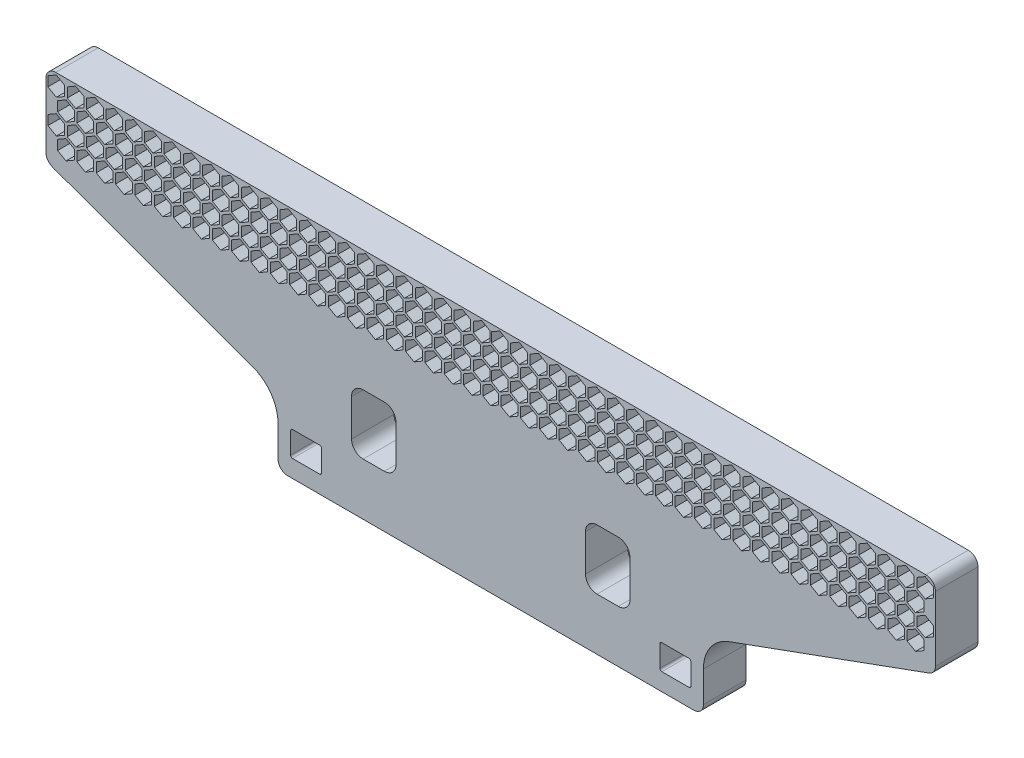
SolidWorks part; units mm, degrees
ref_plane "Front Plane" through (0, 0, 0) normal (0, 0, 1) x (1, 0, 0)
ref_plane "Top Plane" through (0, 0, 0) normal (0, 1, 0) x (1, 0, 0)
ref_plane "Right Plane" through (0, 0, 0) normal (1, 0, 0) x (0, 0, -1)
sketch "Sketch1" plane through (0, 0, 0) normal (0, 0, 1) x (1, 0, 0)
  line L0 (0, 0) -> (0, -38.3146) construction
  line L1 (-69.85, 38.3146) -> (69.85, 38.3146)
  line L2 (-69.85, 38.3146) -> (-69.85, -38.3146)
  line L3 (-69.85, -38.3146) -> (69.85, -38.3146)
  line L4 (69.85, 38.3146) -> (69.85, -38.3146)
  line L5 (-69.85, 38.3146) -> (69.85, -38.3146) construction
  line L6 (-69.85, -38.3146) -> (69.85, 38.3146) construction
  line L7 (65.7225, -32.5996) -> (55.5625, -32.5996)
  line L8 (-65.7225, -24.3446) -> (-55.5625, -24.3446)
  line L9 (-65.7225, -24.3446) -> (-65.7225, -32.5996)
  line L10 (-65.7225, -32.5996) -> (-55.5625, -32.5996)
  line L11 (-55.5625, -24.3446) -> (-55.5625, -32.5996)
  line L12 (-65.7225, -24.3446) -> (-55.5625, -32.5996) construction
  line L13 (-65.7225, -32.5996) -> (-55.5625, -24.3446) construction
  line L14 (55.5625, -24.3446) -> (55.5625, -32.5996)
  line L15 (65.7225, -24.3446) -> (55.5625, -24.3446)
  line L16 (65.7225, -24.3446) -> (65.7225, -32.5996)
  line L17 (41.91, -21.1696) -> (34.925, -21.1696)
  line L18 (-41.91, -1.4846) -> (-34.925, -1.4846)
  line L19 (-45.72, -5.2946) -> (-45.72, -17.3596)
  line L20 (-41.91, -21.1696) -> (-34.925, -21.1696)
  line L21 (-31.115, -5.2946) -> (-31.115, -17.3596)
  line L22 (-45.72, -1.4846) -> (-31.115, -21.1696) construction
  line L23 (-45.72, -21.1696) -> (-31.115, -1.4846) construction
  line L24 (31.115, -5.2946) -> (31.115, -17.3596)
  line L25 (41.91, -1.4846) -> (34.925, -1.4846)
  line L26 (-69.85, 38.3146) -> (-69.85, -38.3146)
  line L27 (69.85, 38.3146) -> (69.85, -38.3146)
  line L28 (45.72, -5.2946) -> (45.72, -17.3596)
  line L29 (69.85, -16.0896) -> (146.05, 11.645)
  line L31 (146.05, 11.645) -> (146.05, 38.3146)
  line L32 (146.05, 38.3146) -> (69.85, 38.3146)
  line L33 (0, -38.3146) -> (0, 38.3146) construction
  line L34 (139.9157, 36.0921) -> (142.6654, 37.6796)
  line L35 (142.6654, 37.6796) -> (145.415, 36.0921)
  line L36 (145.415, 36.0921) -> (145.415, 32.9171)
  line L37 (145.415, 32.9171) -> (142.6654, 31.3296)
  line L38 (142.6654, 31.3296) -> (139.9157, 32.9171)
  line L39 (139.9157, 32.9171) -> (139.9157, 36.0921)
  line L40 (146.05, 11.645) -> (69.85, 11.645) construction
  line L41 (69.85, 11.645) -> (0, 11.645) construction
  line L43 (133.5657, 36.0921) -> (136.3154, 37.6796)
  line L44 (133.5657, 32.9171) -> (133.5657, 36.0921)
  line L45 (136.3154, 31.3296) -> (133.5657, 32.9171)
  line L46 (139.065, 32.9171) -> (136.3154, 31.3296)
  line L47 (139.065, 36.0921) -> (139.065, 32.9171)
  line L48 (136.3154, 37.6796) -> (139.065, 36.0921)
  line L49 (127.2157, 36.0921) -> (129.9654, 37.6796)
  line L50 (127.2157, 32.9171) -> (127.2157, 36.0921)
  line L51 (129.9654, 31.3296) -> (127.2157, 32.9171)
  line L52 (132.715, 32.9171) -> (129.9654, 31.3296)
  line L53 (132.715, 36.0921) -> (132.715, 32.9171)
  line L54 (129.9654, 37.6796) -> (132.715, 36.0921)
  line L55 (120.8657, 36.0921) -> (123.6154, 37.6796)
  line L56 (120.8657, 32.9171) -> (120.8657, 36.0921)
  line L57 (123.6154, 31.3296) -> (120.8657, 32.9171)
  line L58 (126.365, 32.9171) -> (123.6154, 31.3296)
  line L59 (126.365, 36.0921) -> (126.365, 32.9171)
  line L60 (123.6154, 37.6796) -> (126.365, 36.0921)
  line L61 (114.5157, 36.0921) -> (117.2654, 37.6796)
  line L62 (114.5157, 32.9171) -> (114.5157, 36.0921)
  line L63 (117.2654, 31.3296) -> (114.5157, 32.9171)
  line L64 (120.015, 32.9171) -> (117.2654, 31.3296)
  line L65 (120.015, 36.0921) -> (120.015, 32.9171)
  line L66 (117.2654, 37.6796) -> (120.015, 36.0921)
  line L67 (108.1657, 36.0921) -> (110.9154, 37.6796)
  line L68 (108.1657, 32.9171) -> (108.1657, 36.0921)
  line L69 (110.9154, 31.3296) -> (108.1657, 32.9171)
  line L70 (113.665, 32.9171) -> (110.9154, 31.3296)
  line L71 (113.665, 36.0921) -> (113.665, 32.9171)
  line L72 (110.9154, 37.6796) -> (113.665, 36.0921)
  line L73 (101.8157, 36.0921) -> (104.5654, 37.6796)
  line L74 (101.8157, 32.9171) -> (101.8157, 36.0921)
  line L75 (104.5654, 31.3296) -> (101.8157, 32.9171)
  line L76 (107.315, 32.9171) -> (104.5654, 31.3296)
  line L77 (107.315, 36.0921) -> (107.315, 32.9171)
  line L78 (104.5654, 37.6796) -> (107.315, 36.0921)
  line L79 (95.4657, 36.0921) -> (98.2154, 37.6796)
  line L80 (95.4657, 32.9171) -> (95.4657, 36.0921)
  line L81 (98.2154, 31.3296) -> (95.4657, 32.9171)
  line L82 (100.965, 32.9171) -> (98.2154, 31.3296)
  line L83 (100.965, 36.0921) -> (100.965, 32.9171)
  line L84 (98.2154, 37.6796) -> (100.965, 36.0921)
  line L85 (89.1157, 36.0921) -> (91.8654, 37.6796)
  line L86 (89.1157, 32.9171) -> (89.1157, 36.0921)
  line L87 (91.8654, 31.3296) -> (89.1157, 32.9171)
  line L88 (94.615, 32.9171) -> (91.8654, 31.3296)
  line L89 (94.615, 36.0921) -> (94.615, 32.9171)
  line L90 (91.8654, 37.6796) -> (94.615, 36.0921)
  line L91 (82.7657, 36.0921) -> (85.5154, 37.6796)
  line L92 (82.7657, 32.9171) -> (82.7657, 36.0921)
  line L93 (85.5154, 31.3296) -> (82.7657, 32.9171)
  line L94 (88.265, 32.9171) -> (85.5154, 31.3296)
  line L95 (88.265, 36.0921) -> (88.265, 32.9171)
  line L96 (85.5154, 37.6796) -> (88.265, 36.0921)
  line L97 (76.4157, 36.0921) -> (79.1654, 37.6796)
  line L98 (76.4157, 32.9171) -> (76.4157, 36.0921)
  line L99 (79.1654, 31.3296) -> (76.4157, 32.9171)
  line L100 (81.915, 32.9171) -> (79.1654, 31.3296)
  line L101 (81.915, 36.0921) -> (81.915, 32.9171)
  line L102 (79.1654, 37.6796) -> (81.915, 36.0921)
  line L103 (70.0657, 36.0921) -> (72.8154, 37.6796)
  line L104 (70.0657, 32.9171) -> (70.0657, 36.0921)
  line L105 (72.8154, 31.3296) -> (70.0657, 32.9171)
  line L106 (75.565, 32.9171) -> (72.8154, 31.3296)
  line L107 (75.565, 36.0921) -> (75.565, 32.9171)
  line L108 (72.8154, 37.6796) -> (75.565, 36.0921)
  line L109 (63.7157, 36.0921) -> (66.4654, 37.6796)
  line L110 (63.7157, 32.9171) -> (63.7157, 36.0921)
  line L111 (66.4654, 31.3296) -> (63.7157, 32.9171)
  line L112 (69.215, 32.9171) -> (66.4654, 31.3296)
  line L113 (69.215, 36.0921) -> (69.215, 32.9171)
  line L114 (66.4654, 37.6796) -> (69.215, 36.0921)
  line L115 (57.3657, 36.0921) -> (60.1154, 37.6796)
  line L116 (57.3657, 32.9171) -> (57.3657, 36.0921)
  line L117 (60.1154, 31.3296) -> (57.3657, 32.9171)
  line L118 (62.865, 32.9171) -> (60.1154, 31.3296)
  line L119 (62.865, 36.0921) -> (62.865, 32.9171)
  line L120 (60.1154, 37.6796) -> (62.865, 36.0921)
  line L121 (51.0157, 36.0921) -> (53.7654, 37.6796)
  line L122 (51.0157, 32.9171) -> (51.0157, 36.0921)
  line L123 (53.7654, 31.3296) -> (51.0157, 32.9171)
  line L124 (56.515, 32.9171) -> (53.7654, 31.3296)
  line L125 (56.515, 36.0921) -> (56.515, 32.9171)
  line L126 (53.7654, 37.6796) -> (56.515, 36.0921)
  line L127 (44.6657, 36.0921) -> (47.4154, 37.6796)
  line L128 (44.6657, 32.9171) -> (44.6657, 36.0921)
  line L129 (47.4154, 31.3296) -> (44.6657, 32.9171)
  line L130 (50.165, 32.9171) -> (47.4154, 31.3296)
  line L131 (50.165, 36.0921) -> (50.165, 32.9171)
  line L132 (47.4154, 37.6796) -> (50.165, 36.0921)
  line L133 (38.3157, 36.0921) -> (41.0654, 37.6796)
  line L134 (38.3157, 32.9171) -> (38.3157, 36.0921)
  line L135 (41.0654, 31.3296) -> (38.3157, 32.9171)
  line L136 (43.815, 32.9171) -> (41.0654, 31.3296)
  line L137 (43.815, 36.0921) -> (43.815, 32.9171)
  line L138 (41.0654, 37.6796) -> (43.815, 36.0921)
  line L139 (31.9657, 36.0921) -> (34.7154, 37.6796)
  line L140 (31.9657, 32.9171) -> (31.9657, 36.0921)
  line L141 (34.7154, 31.3296) -> (31.9657, 32.9171)
  line L142 (37.465, 32.9171) -> (34.7154, 31.3296)
  line L143 (37.465, 36.0921) -> (37.465, 32.9171)
  line L144 (34.7154, 37.6796) -> (37.465, 36.0921)
  line L145 (25.6157, 36.0921) -> (28.3654, 37.6796)
  line L146 (25.6157, 32.9171) -> (25.6157, 36.0921)
  line L147 (28.3654, 31.3296) -> (25.6157, 32.9171)
  line L148 (31.115, 32.9171) -> (28.3654, 31.3296)
  line L149 (31.115, 36.0921) -> (31.115, 32.9171)
  line L150 (28.3654, 37.6796) -> (31.115, 36.0921)
  line L151 (19.2657, 36.0921) -> (22.0154, 37.6796)
  line L152 (19.2657, 32.9171) -> (19.2657, 36.0921)
  line L153 (22.0154, 31.3296) -> (19.2657, 32.9171)
  line L154 (24.765, 32.9171) -> (22.0154, 31.3296)
  line L155 (24.765, 36.0921) -> (24.765, 32.9171)
  line L156 (22.0154, 37.6796) -> (24.765, 36.0921)
  line L157 (12.9157, 36.0921) -> (15.6654, 37.6796)
  line L158 (12.9157, 32.9171) -> (12.9157, 36.0921)
  line L159 (15.6654, 31.3296) -> (12.9157, 32.9171)
  line L160 (18.415, 32.9171) -> (15.6654, 31.3296)
  line L161 (18.415, 36.0921) -> (18.415, 32.9171)
  line L162 (15.6654, 37.6796) -> (18.415, 36.0921)
  line L163 (6.5657, 36.0921) -> (9.3154, 37.6796)
  line L164 (6.5657, 32.9171) -> (6.5657, 36.0921)
  line L165 (9.3154, 31.3296) -> (6.5657, 32.9171)
  line L166 (12.065, 32.9171) -> (9.3154, 31.3296)
  line L167 (12.065, 36.0921) -> (12.065, 32.9171)
  line L168 (9.3154, 37.6796) -> (12.065, 36.0921)
  line L169 (0.2157, 36.0921) -> (2.9654, 37.6796)
  line L170 (0.2157, 32.9171) -> (0.2157, 36.0921)
  line L171 (2.9654, 31.3296) -> (0.2157, 32.9171)
  line L172 (5.715, 32.9171) -> (2.9654, 31.3296)
  line L173 (5.715, 36.0921) -> (5.715, 32.9171)
  line L174 (2.9654, 37.6796) -> (5.715, 36.0921)
  line L175 (136.7407, 30.5928) -> (139.4904, 32.1803)
  line L176 (136.7407, 27.4178) -> (136.7407, 30.5928)
  line L177 (139.4904, 25.8303) -> (136.7407, 27.4178)
  line L178 (142.24, 27.4178) -> (139.4904, 25.8303)
  line L179 (142.24, 30.5928) -> (142.24, 27.4178)
  line L180 (139.4904, 32.1803) -> (142.24, 30.5928)
  line L181 (135.89, 27.4178) -> (133.1404, 25.8303)
  line L182 (133.1404, 25.8303) -> (130.3907, 27.4178)
  line L183 (130.3907, 27.4178) -> (130.3907, 30.5928)
  line L184 (135.89, 30.5928) -> (135.89, 27.4178)
  line L185 (133.1404, 32.1803) -> (135.89, 30.5928)
  line L186 (130.3907, 30.5928) -> (133.1404, 32.1803)
  line L187 (129.54, 27.4178) -> (126.7904, 25.8303)
  line L188 (126.7904, 25.8303) -> (124.0407, 27.4178)
  line L189 (124.0407, 27.4178) -> (124.0407, 30.5928)
  line L190 (129.54, 30.5928) -> (129.54, 27.4178)
  line L191 (126.7904, 32.1803) -> (129.54, 30.5928)
  line L192 (124.0407, 30.5928) -> (126.7904, 32.1803)
  line L193 (123.19, 27.4178) -> (120.4404, 25.8303)
  line L194 (120.4404, 25.8303) -> (117.6907, 27.4178)
  line L195 (117.6907, 27.4178) -> (117.6907, 30.5928)
  line L196 (123.19, 30.5928) -> (123.19, 27.4178)
  line L197 (120.4404, 32.1803) -> (123.19, 30.5928)
  line L198 (117.6907, 30.5928) -> (120.4404, 32.1803)
  line L199 (116.84, 27.4178) -> (114.0904, 25.8303)
  line L200 (114.0904, 25.8303) -> (111.3407, 27.4178)
  line L201 (111.3407, 27.4178) -> (111.3407, 30.5928)
  line L202 (116.84, 30.5928) -> (116.84, 27.4178)
  line L203 (114.0904, 32.1803) -> (116.84, 30.5928)
  line L204 (111.3407, 30.5928) -> (114.0904, 32.1803)
  line L205 (110.49, 27.4178) -> (107.7404, 25.8303)
  line L206 (107.7404, 25.8303) -> (104.9907, 27.4178)
  line L207 (104.9907, 27.4178) -> (104.9907, 30.5928)
  line L208 (110.49, 30.5928) -> (110.49, 27.4178)
  line L209 (107.7404, 32.1803) -> (110.49, 30.5928)
  line L210 (104.9907, 30.5928) -> (107.7404, 32.1803)
  line L211 (104.14, 27.4178) -> (101.3904, 25.8303)
  line L212 (101.3904, 25.8303) -> (98.6407, 27.4178)
  line L213 (98.6407, 27.4178) -> (98.6407, 30.5928)
  line L214 (104.14, 30.5928) -> (104.14, 27.4178)
  line L215 (101.3904, 32.1803) -> (104.14, 30.5928)
  line L216 (98.6407, 30.5928) -> (101.3904, 32.1803)
  line L217 (97.79, 27.4178) -> (95.0404, 25.8303)
  line L218 (95.0404, 25.8303) -> (92.2907, 27.4178)
  line L219 (92.2907, 27.4178) -> (92.2907, 30.5928)
  line L220 (97.79, 30.5928) -> (97.79, 27.4178)
  line L221 (95.0404, 32.1803) -> (97.79, 30.5928)
  line L222 (92.2907, 30.5928) -> (95.0404, 32.1803)
  line L223 (91.44, 27.4178) -> (88.6904, 25.8303)
  line L224 (88.6904, 25.8303) -> (85.9407, 27.4178)
  line L225 (85.9407, 27.4178) -> (85.9407, 30.5928)
  line L226 (91.44, 30.5928) -> (91.44, 27.4178)
  line L227 (88.6904, 32.1803) -> (91.44, 30.5928)
  line L228 (85.9407, 30.5928) -> (88.6904, 32.1803)
  line L229 (85.09, 27.4178) -> (82.3404, 25.8303)
  line L230 (82.3404, 25.8303) -> (79.5907, 27.4178)
  line L231 (79.5907, 27.4178) -> (79.5907, 30.5928)
  line L232 (85.09, 30.5928) -> (85.09, 27.4178)
  line L233 (82.3404, 32.1803) -> (85.09, 30.5928)
  line L234 (79.5907, 30.5928) -> (82.3404, 32.1803)
  line L235 (78.74, 27.4178) -> (75.9904, 25.8303)
  line L236 (75.9904, 25.8303) -> (73.2407, 27.4178)
  line L237 (73.2407, 27.4178) -> (73.2407, 30.5928)
  line L238 (78.74, 30.5928) -> (78.74, 27.4178)
  line L239 (75.9904, 32.1803) -> (78.74, 30.5928)
  line L240 (73.2407, 30.5928) -> (75.9904, 32.1803)
  line L241 (72.39, 27.4178) -> (69.6404, 25.8303)
  line L242 (69.6404, 25.8303) -> (66.8907, 27.4178)
  line L243 (66.8907, 27.4178) -> (66.8907, 30.5928)
  line L244 (72.39, 30.5928) -> (72.39, 27.4178)
  line L245 (69.6404, 32.1803) -> (72.39, 30.5928)
  line L246 (66.8907, 30.5928) -> (69.6404, 32.1803)
  line L247 (66.04, 27.4178) -> (63.2904, 25.8303)
  line L248 (63.2904, 25.8303) -> (60.5407, 27.4178)
  line L249 (60.5407, 27.4178) -> (60.5407, 30.5928)
  line L250 (66.04, 30.5928) -> (66.04, 27.4178)
  line L251 (63.2904, 32.1803) -> (66.04, 30.5928)
  line L252 (60.5407, 30.5928) -> (63.2904, 32.1803)
  line L253 (59.69, 27.4178) -> (56.9404, 25.8303)
  line L254 (56.9404, 25.8303) -> (54.1907, 27.4178)
  line L255 (54.1907, 27.4178) -> (54.1907, 30.5928)
  line L256 (59.69, 30.5928) -> (59.69, 27.4178)
  line L257 (56.9404, 32.1803) -> (59.69, 30.5928)
  line L258 (54.1907, 30.5928) -> (56.9404, 32.1803)
  line L259 (53.34, 27.4178) -> (50.5904, 25.8303)
  line L260 (50.5904, 25.8303) -> (47.8407, 27.4178)
  line L261 (47.8407, 27.4178) -> (47.8407, 30.5928)
  line L262 (53.34, 30.5928) -> (53.34, 27.4178)
  line L263 (50.5904, 32.1803) -> (53.34, 30.5928)
  line L264 (47.8407, 30.5928) -> (50.5904, 32.1803)
  line L265 (46.99, 27.4178) -> (44.2404, 25.8303)
  line L266 (44.2404, 25.8303) -> (41.4907, 27.4178)
  line L267 (41.4907, 27.4178) -> (41.4907, 30.5928)
  line L268 (46.99, 30.5928) -> (46.99, 27.4178)
  line L269 (44.2404, 32.1803) -> (46.99, 30.5928)
  line L270 (41.4907, 30.5928) -> (44.2404, 32.1803)
  line L271 (40.64, 27.4178) -> (37.8904, 25.8303)
  line L272 (37.8904, 25.8303) -> (35.1407, 27.4178)
  line L273 (35.1407, 27.4178) -> (35.1407, 30.5928)
  line L274 (40.64, 30.5928) -> (40.64, 27.4178)
  line L275 (37.8904, 32.1803) -> (40.64, 30.5928)
  line L276 (35.1407, 30.5928) -> (37.8904, 32.1803)
  line L277 (34.29, 27.4178) -> (31.5404, 25.8303)
  line L278 (31.5404, 25.8303) -> (28.7907, 27.4178)
  line L279 (28.7907, 27.4178) -> (28.7907, 30.5928)
  line L280 (34.29, 30.5928) -> (34.29, 27.4178)
  line L281 (31.5404, 32.1803) -> (34.29, 30.5928)
  line L282 (28.7907, 30.5928) -> (31.5404, 32.1803)
  line L283 (27.94, 27.4178) -> (25.1904, 25.8303)
  line L284 (25.1904, 25.8303) -> (22.4407, 27.4178)
  line L285 (22.4407, 27.4178) -> (22.4407, 30.5928)
  line L286 (27.94, 30.5928) -> (27.94, 27.4178)
  line L287 (25.1904, 32.1803) -> (27.94, 30.5928)
  line L288 (22.4407, 30.5928) -> (25.1904, 32.1803)
  line L289 (21.59, 27.4178) -> (18.8404, 25.8303)
  line L290 (18.8404, 25.8303) -> (16.0907, 27.4178)
  line L291 (16.0907, 27.4178) -> (16.0907, 30.5928)
  line L292 (21.59, 30.5928) -> (21.59, 27.4178)
  line L293 (18.8404, 32.1803) -> (21.59, 30.5928)
  line L294 (16.0907, 30.5928) -> (18.8404, 32.1803)
  line L295 (15.24, 27.4178) -> (12.4904, 25.8303)
  line L296 (12.4904, 25.8303) -> (9.7407, 27.4178)
  line L297 (9.7407, 27.4178) -> (9.7407, 30.5928)
  line L298 (15.24, 30.5928) -> (15.24, 27.4178)
  line L299 (12.4904, 32.1803) -> (15.24, 30.5928)
  line L300 (9.7407, 30.5928) -> (12.4904, 32.1803)
  line L301 (8.89, 27.4178) -> (6.1404, 25.8303)
  line L302 (6.1404, 25.8303) -> (3.3907, 27.4178)
  line L303 (3.3907, 27.4178) -> (3.3907, 30.5928)
  line L304 (8.89, 30.5928) -> (8.89, 27.4178)
  line L305 (6.1404, 32.1803) -> (8.89, 30.5928)
  line L306 (3.3907, 30.5928) -> (6.1404, 32.1803)
  line L307 (2.54, 27.4178) -> (-0.2096, 25.8303)
  line L308 (-0.2096, 25.8303) -> (-2.9593, 27.4178)
  line L309 (-2.9593, 27.4178) -> (-2.9593, 30.5928)
  line L310 (2.54, 30.5928) -> (2.54, 27.4178)
  line L311 (-0.2096, 32.1803) -> (2.54, 30.5928)
  line L312 (-2.9593, 30.5928) -> (-0.2096, 32.1803)
  line L313 (69.85, 27.3042) -> (69.85, -49.3249)
  line L314 (69.85, 27.3042) -> (69.85, -49.3249)
  line L315 (139.9157, 25.0817) -> (142.6654, 26.6692)
  line L316 (142.6654, 26.6692) -> (145.415, 25.0817)
  line L317 (145.415, 21.9067) -> (142.6654, 20.3192)
  line L318 (142.6654, 20.3192) -> (139.9157, 21.9067)
  line L319 (139.9157, 21.9067) -> (139.9157, 25.0817)
  line L320 (133.5657, 25.0817) -> (136.3154, 26.6692)
  line L321 (133.5657, 21.9067) -> (133.5657, 25.0817)
  line L322 (136.3154, 20.3192) -> (133.5657, 21.9067)
  line L323 (139.065, 21.9067) -> (136.3154, 20.3192)
  line L324 (139.065, 25.0817) -> (139.065, 21.9067)
  line L325 (136.3154, 26.6692) -> (139.065, 25.0817)
  line L326 (127.2157, 25.0817) -> (129.9654, 26.6692)
  line L327 (127.2157, 21.9067) -> (127.2157, 25.0817)
  line L328 (129.9654, 20.3192) -> (127.2157, 21.9067)
  line L329 (132.715, 21.9067) -> (129.9654, 20.3192)
  line L330 (132.715, 25.0817) -> (132.715, 21.9067)
  line L331 (129.9654, 26.6692) -> (132.715, 25.0817)
  line L332 (120.8657, 25.0817) -> (123.6154, 26.6692)
  line L333 (120.8657, 21.9067) -> (120.8657, 25.0817)
  line L334 (123.6154, 20.3192) -> (120.8657, 21.9067)
  line L335 (126.365, 21.9067) -> (123.6154, 20.3192)
  line L336 (126.365, 25.0817) -> (126.365, 21.9067)
  line L337 (123.6154, 26.6692) -> (126.365, 25.0817)
  line L338 (114.5157, 25.0817) -> (117.2654, 26.6692)
  line L339 (114.5157, 21.9067) -> (114.5157, 25.0817)
  line L340 (117.2654, 20.3192) -> (114.5157, 21.9067)
  line L341 (120.015, 21.9067) -> (117.2654, 20.3192)
  line L342 (120.015, 25.0817) -> (120.015, 21.9067)
  line L343 (117.2654, 26.6692) -> (120.015, 25.0817)
  line L344 (108.1657, 25.0817) -> (110.9154, 26.6692)
  line L345 (108.1657, 21.9067) -> (108.1657, 25.0817)
  line L346 (110.9154, 20.3192) -> (108.1657, 21.9067)
  line L347 (113.665, 21.9067) -> (110.9154, 20.3192)
  line L348 (113.665, 25.0817) -> (113.665, 21.9067)
  line L349 (110.9154, 26.6692) -> (113.665, 25.0817)
  line L350 (101.8157, 25.0817) -> (104.5654, 26.6692)
  line L351 (101.8157, 21.9067) -> (101.8157, 25.0817)
  line L352 (104.5654, 20.3192) -> (101.8157, 21.9067)
  line L353 (107.315, 21.9067) -> (104.5654, 20.3192)
  line L354 (107.315, 25.0817) -> (107.315, 21.9067)
  line L355 (104.5654, 26.6692) -> (107.315, 25.0817)
  line L356 (95.4657, 25.0817) -> (98.2154, 26.6692)
  line L357 (95.4657, 21.9067) -> (95.4657, 25.0817)
  line L358 (98.2154, 20.3192) -> (95.4657, 21.9067)
  line L359 (100.965, 21.9067) -> (98.2154, 20.3192)
  line L360 (100.965, 25.0817) -> (100.965, 21.9067)
  line L361 (98.2154, 26.6692) -> (100.965, 25.0817)
  line L362 (89.1157, 25.0817) -> (91.8654, 26.6692)
  line L363 (89.1157, 21.9067) -> (89.1157, 25.0817)
  line L364 (91.8654, 20.3192) -> (89.1157, 21.9067)
  line L365 (94.615, 21.9067) -> (91.8654, 20.3192)
  line L366 (94.615, 25.0817) -> (94.615, 21.9067)
  line L367 (91.8654, 26.6692) -> (94.615, 25.0817)
  line L368 (82.7657, 25.0817) -> (85.5154, 26.6692)
  line L369 (82.7657, 21.9067) -> (82.7657, 25.0817)
  line L370 (85.5154, 20.3192) -> (82.7657, 21.9067)
  line L371 (88.265, 21.9067) -> (85.5154, 20.3192)
  line L372 (88.265, 25.0817) -> (88.265, 21.9067)
  line L373 (85.5154, 26.6692) -> (88.265, 25.0817)
  line L374 (76.4157, 25.0817) -> (79.1654, 26.6692)
  line L375 (76.4157, 21.9067) -> (76.4157, 25.0817)
  line L376 (79.1654, 20.3192) -> (76.4157, 21.9067)
  line L377 (81.915, 21.9067) -> (79.1654, 20.3192)
  line L378 (81.915, 25.0817) -> (81.915, 21.9067)
  line L379 (79.1654, 26.6692) -> (81.915, 25.0817)
  line L380 (70.0657, 25.0817) -> (72.8154, 26.6692)
  line L381 (70.0657, 21.9067) -> (70.0657, 25.0817)
  line L382 (72.8154, 20.3192) -> (70.0657, 21.9067)
  line L383 (75.565, 21.9067) -> (72.8154, 20.3192)
  line L384 (75.565, 25.0817) -> (75.565, 21.9067)
  line L385 (72.8154, 26.6692) -> (75.565, 25.0817)
  line L386 (63.7157, 25.0817) -> (66.4654, 26.6692)
  line L387 (63.7157, 21.9067) -> (63.7157, 25.0817)
  line L388 (66.4654, 20.3192) -> (63.7157, 21.9067)
  line L389 (69.215, 21.9067) -> (66.4654, 20.3192)
  line L390 (69.215, 25.0817) -> (69.215, 21.9067)
  line L391 (66.4654, 26.6692) -> (69.215, 25.0817)
  line L392 (57.3657, 25.0817) -> (60.1154, 26.6692)
  line L393 (57.3657, 21.9067) -> (57.3657, 25.0817)
  line L394 (60.1154, 20.3192) -> (57.3657, 21.9067)
  line L395 (62.865, 21.9067) -> (60.1154, 20.3192)
  line L396 (62.865, 25.0817) -> (62.865, 21.9067)
  line L397 (60.1154, 26.6692) -> (62.865, 25.0817)
  line L398 (51.0157, 25.0817) -> (53.7654, 26.6692)
  line L399 (51.0157, 21.9067) -> (51.0157, 25.0817)
  line L400 (53.7654, 20.3192) -> (51.0157, 21.9067)
  line L401 (56.515, 21.9067) -> (53.7654, 20.3192)
  line L402 (56.515, 25.0817) -> (56.515, 21.9067)
  line L403 (53.7654, 26.6692) -> (56.515, 25.0817)
  line L404 (44.6657, 25.0817) -> (47.4154, 26.6692)
  line L405 (44.6657, 21.9067) -> (44.6657, 25.0817)
  line L406 (47.4154, 20.3192) -> (44.6657, 21.9067)
  line L407 (50.165, 21.9067) -> (47.4154, 20.3192)
  line L408 (50.165, 25.0817) -> (50.165, 21.9067)
  line L409 (47.4154, 26.6692) -> (50.165, 25.0817)
  line L410 (38.3157, 25.0817) -> (41.0654, 26.6692)
  line L411 (38.3157, 21.9067) -> (38.3157, 25.0817)
  line L412 (41.0654, 20.3192) -> (38.3157, 21.9067)
  line L413 (43.815, 21.9067) -> (41.0654, 20.3192)
  line L414 (43.815, 25.0817) -> (43.815, 21.9067)
  line L415 (41.0654, 26.6692) -> (43.815, 25.0817)
  line L416 (31.9657, 25.0817) -> (34.7154, 26.6692)
  line L417 (31.9657, 21.9067) -> (31.9657, 25.0817)
  line L418 (34.7154, 20.3192) -> (31.9657, 21.9067)
  line L419 (37.465, 21.9067) -> (34.7154, 20.3192)
  line L420 (37.465, 25.0817) -> (37.465, 21.9067)
  line L421 (34.7154, 26.6692) -> (37.465, 25.0817)
  line L422 (25.6157, 25.0817) -> (28.3654, 26.6692)
  line L423 (25.6157, 21.9067) -> (25.6157, 25.0817)
  line L424 (28.3654, 20.3192) -> (25.6157, 21.9067)
  line L425 (31.115, 21.9067) -> (28.3654, 20.3192)
  line L426 (31.115, 25.0817) -> (31.115, 21.9067)
  line L427 (28.3654, 26.6692) -> (31.115, 25.0817)
  line L428 (19.2657, 25.0817) -> (22.0154, 26.6692)
  line L429 (19.2657, 21.9067) -> (19.2657, 25.0817)
  line L430 (22.0154, 20.3192) -> (19.2657, 21.9067)
  line L431 (24.765, 21.9067) -> (22.0154, 20.3192)
  line L432 (24.765, 25.0817) -> (24.765, 21.9067)
  line L433 (22.0154, 26.6692) -> (24.765, 25.0817)
  line L434 (12.9157, 25.0817) -> (15.6654, 26.6692)
  line L435 (12.9157, 21.9067) -> (12.9157, 25.0817)
  line L436 (15.6654, 20.3192) -> (12.9157, 21.9067)
  line L437 (18.415, 21.9067) -> (15.6654, 20.3192)
  line L438 (18.415, 25.0817) -> (18.415, 21.9067)
  line L439 (15.6654, 26.6692) -> (18.415, 25.0817)
  line L440 (6.5657, 25.0817) -> (9.3154, 26.6692)
  line L441 (6.5657, 21.9067) -> (6.5657, 25.0817)
  line L442 (9.3154, 20.3192) -> (6.5657, 21.9067)
  line L443 (12.065, 21.9067) -> (9.3154, 20.3192)
  line L444 (12.065, 25.0817) -> (12.065, 21.9067)
  line L445 (9.3154, 26.6692) -> (12.065, 25.0817)
  line L446 (0.2157, 25.0817) -> (2.9654, 26.6692)
  line L447 (0.2157, 21.9067) -> (0.2157, 25.0817)
  line L448 (2.9654, 20.3192) -> (0.2157, 21.9067)
  line L449 (5.715, 21.9067) -> (2.9654, 20.3192)
  line L450 (5.715, 25.0817) -> (5.715, 21.9067)
  line L451 (2.9654, 26.6692) -> (5.715, 25.0817)
  line L452 (136.7407, 19.5825) -> (139.4904, 21.17)
  line L453 (136.7407, 16.4075) -> (136.7407, 19.5825)
  line L454 (139.4904, 14.82) -> (136.7407, 16.4075)
  line L455 (142.24, 16.4075) -> (139.4904, 14.82)
  line L456 (142.24, 19.5825) -> (142.24, 16.4075)
  line L457 (139.4904, 21.17) -> (142.24, 19.5825)
  line L458 (135.89, 16.4075) -> (133.1404, 14.82)
  line L459 (133.1404, 14.82) -> (130.3907, 16.4075)
  line L460 (130.3907, 16.4075) -> (130.3907, 19.5825)
  line L461 (135.89, 19.5825) -> (135.89, 16.4075)
  line L462 (133.1404, 21.17) -> (135.89, 19.5825)
  line L463 (130.3907, 19.5825) -> (133.1404, 21.17)
  line L464 (129.54, 16.4075) -> (126.7904, 14.82)
  line L465 (126.7904, 14.82) -> (124.0407, 16.4075)
  line L466 (124.0407, 16.4075) -> (124.0407, 19.5825)
  line L467 (129.54, 19.5825) -> (129.54, 16.4075)
  line L468 (126.7904, 21.17) -> (129.54, 19.5825)
  line L469 (124.0407, 19.5825) -> (126.7904, 21.17)
  line L470 (123.19, 16.4075) -> (120.4404, 14.82)
  line L471 (120.4404, 14.82) -> (117.6907, 16.4075)
  line L472 (117.6907, 16.4075) -> (117.6907, 19.5825)
  line L473 (123.19, 19.5825) -> (123.19, 16.4075)
  line L474 (120.4404, 21.17) -> (123.19, 19.5825)
  line L475 (117.6907, 19.5825) -> (120.4404, 21.17)
  line L476 (116.84, 16.4075) -> (114.0904, 14.82)
  line L477 (114.0904, 14.82) -> (111.3407, 16.4075)
  line L478 (111.3407, 16.4075) -> (111.3407, 19.5825)
  line L479 (116.84, 19.5825) -> (116.84, 16.4075)
  line L480 (114.0904, 21.17) -> (116.84, 19.5825)
  line L481 (111.3407, 19.5825) -> (114.0904, 21.17)
  line L482 (110.49, 16.4075) -> (107.7404, 14.82)
  line L483 (107.7404, 14.82) -> (104.9907, 16.4075)
  line L484 (104.9907, 16.4075) -> (104.9907, 19.5825)
  line L485 (110.49, 19.5825) -> (110.49, 16.4075)
  line L486 (107.7404, 21.17) -> (110.49, 19.5825)
  line L487 (104.9907, 19.5825) -> (107.7404, 21.17)
  line L488 (104.14, 16.4075) -> (101.3904, 14.82)
  line L489 (101.3904, 14.82) -> (98.6407, 16.4075)
  line L490 (98.6407, 16.4075) -> (98.6407, 19.5825)
  line L491 (104.14, 19.5825) -> (104.14, 16.4075)
  line L492 (101.3904, 21.17) -> (104.14, 19.5825)
  line L493 (98.6407, 19.5825) -> (101.3904, 21.17)
  line L494 (97.79, 16.4075) -> (95.0404, 14.82)
  line L495 (95.0404, 14.82) -> (92.2907, 16.4075)
  line L496 (92.2907, 16.4075) -> (92.2907, 19.5825)
  line L497 (97.79, 19.5825) -> (97.79, 16.4075)
  line L498 (95.0404, 21.17) -> (97.79, 19.5825)
  line L499 (92.2907, 19.5825) -> (95.0404, 21.17)
  line L500 (91.44, 16.4075) -> (88.6904, 14.82)
  line L501 (88.6904, 14.82) -> (85.9407, 16.4075)
  line L502 (85.9407, 16.4075) -> (85.9407, 19.5825)
  line L503 (91.44, 19.5825) -> (91.44, 16.4075)
  line L504 (88.6904, 21.17) -> (91.44, 19.5825)
  line L505 (85.9407, 19.5825) -> (88.6904, 21.17)
  line L506 (85.09, 16.4075) -> (82.3404, 14.82)
  line L507 (82.3404, 14.82) -> (79.5907, 16.4075)
  line L508 (79.5907, 16.4075) -> (79.5907, 19.5825)
  line L509 (85.09, 19.5825) -> (85.09, 16.4075)
  line L510 (82.3404, 21.17) -> (85.09, 19.5825)
  line L511 (79.5907, 19.5825) -> (82.3404, 21.17)
  line L512 (78.74, 16.4075) -> (75.9904, 14.82)
  line L513 (75.9904, 14.82) -> (73.2407, 16.4075)
  line L514 (73.2407, 16.4075) -> (73.2407, 19.5825)
  line L515 (78.74, 19.5825) -> (78.74, 16.4075)
  line L516 (75.9904, 21.17) -> (78.74, 19.5825)
  line L517 (73.2407, 19.5825) -> (75.9904, 21.17)
  line L518 (72.39, 16.4075) -> (69.6404, 14.82)
  line L519 (69.6404, 14.82) -> (66.8907, 16.4075)
  line L520 (66.8907, 16.4075) -> (66.8907, 19.5825)
  line L521 (72.39, 19.5825) -> (72.39, 16.4075)
  line L522 (69.6404, 21.17) -> (72.39, 19.5825)
  line L523 (66.8907, 19.5825) -> (69.6404, 21.17)
  line L524 (66.04, 16.4075) -> (63.2904, 14.82)
  line L525 (63.2904, 14.82) -> (60.5407, 16.4075)
  line L526 (60.5407, 16.4075) -> (60.5407, 19.5825)
  line L527 (66.04, 19.5825) -> (66.04, 16.4075)
  line L528 (63.2904, 21.17) -> (66.04, 19.5825)
  line L529 (60.5407, 19.5825) -> (63.2904, 21.17)
  line L530 (59.69, 16.4075) -> (56.9404, 14.82)
  line L531 (56.9404, 14.82) -> (54.1907, 16.4075)
  line L532 (54.1907, 16.4075) -> (54.1907, 19.5825)
  line L533 (59.69, 19.5825) -> (59.69, 16.4075)
  line L534 (56.9404, 21.17) -> (59.69, 19.5825)
  line L535 (54.1907, 19.5825) -> (56.9404, 21.17)
  line L536 (53.34, 16.4075) -> (50.5904, 14.82)
  line L537 (50.5904, 14.82) -> (47.8407, 16.4075)
  line L538 (47.8407, 16.4075) -> (47.8407, 19.5825)
  line L539 (53.34, 19.5825) -> (53.34, 16.4075)
  line L540 (50.5904, 21.17) -> (53.34, 19.5825)
  line L541 (47.8407, 19.5825) -> (50.5904, 21.17)
  line L542 (46.99, 16.4075) -> (44.2404, 14.82)
  line L543 (44.2404, 14.82) -> (41.4907, 16.4075)
  line L544 (41.4907, 16.4075) -> (41.4907, 19.5825)
  line L545 (46.99, 19.5825) -> (46.99, 16.4075)
  line L546 (44.2404, 21.17) -> (46.99, 19.5825)
  line L547 (41.4907, 19.5825) -> (44.2404, 21.17)
  line L548 (40.64, 16.4075) -> (37.8904, 14.82)
  line L549 (37.8904, 14.82) -> (35.1407, 16.4075)
  line L550 (35.1407, 16.4075) -> (35.1407, 19.5825)
  line L551 (40.64, 19.5825) -> (40.64, 16.4075)
  line L552 (37.8904, 21.17) -> (40.64, 19.5825)
  line L553 (35.1407, 19.5825) -> (37.8904, 21.17)
  line L554 (34.29, 16.4075) -> (31.5404, 14.82)
  line L555 (31.5404, 14.82) -> (28.7907, 16.4075)
  line L556 (28.7907, 16.4075) -> (28.7907, 19.5825)
  line L557 (34.29, 19.5825) -> (34.29, 16.4075)
  line L558 (31.5404, 21.17) -> (34.29, 19.5825)
  line L559 (28.7907, 19.5825) -> (31.5404, 21.17)
  line L560 (27.94, 16.4075) -> (25.1904, 14.82)
  line L561 (25.1904, 14.82) -> (22.4407, 16.4075)
  line L562 (22.4407, 16.4075) -> (22.4407, 19.5825)
  line L563 (27.94, 19.5825) -> (27.94, 16.4075)
  line L564 (25.1904, 21.17) -> (27.94, 19.5825)
  line L565 (22.4407, 19.5825) -> (25.1904, 21.17)
  line L566 (21.59, 16.4075) -> (18.8404, 14.82)
  line L567 (18.8404, 14.82) -> (16.0907, 16.4075)
  line L568 (16.0907, 16.4075) -> (16.0907, 19.5825)
  line L569 (21.59, 19.5825) -> (21.59, 16.4075)
  line L570 (18.8404, 21.17) -> (21.59, 19.5825)
  line L571 (16.0907, 19.5825) -> (18.8404, 21.17)
  line L572 (15.24, 16.4075) -> (12.4904, 14.82)
  line L573 (12.4904, 14.82) -> (9.7407, 16.4075)
  line L574 (9.7407, 16.4075) -> (9.7407, 19.5825)
  line L575 (15.24, 19.5825) -> (15.24, 16.4075)
  line L576 (12.4904, 21.17) -> (15.24, 19.5825)
  line L577 (9.7407, 19.5825) -> (12.4904, 21.17)
  line L578 (8.89, 16.4075) -> (6.1404, 14.82)
  line L579 (6.1404, 14.82) -> (3.3907, 16.4075)
  line L580 (3.3907, 16.4075) -> (3.3907, 19.5825)
  line L581 (8.89, 19.5825) -> (8.89, 16.4075)
  line L582 (6.1404, 21.17) -> (8.89, 19.5825)
  line L583 (3.3907, 19.5825) -> (6.1404, 21.17)
  line L584 (2.54, 16.4075) -> (-0.2096, 14.82)
  line L585 (-0.2096, 14.82) -> (-2.9593, 16.4075)
  line L586 (-2.9593, 16.4075) -> (-2.9593, 19.5825)
  line L587 (2.54, 19.5825) -> (2.54, 16.4075)
  line L588 (-0.2096, 21.17) -> (2.54, 19.5825)
  line L589 (-2.9593, 19.5825) -> (-0.2096, 21.17)
  line L590 (-69.85, -49.3249) -> (69.85, 27.3042) construction
  line L591 (0, -49.3249) -> (0, 27.3042) construction
  line L592 (145.415, 25.0817) -> (145.415, 21.9067)
  line L593 (0, 38.3146) -> (0, -38.3146)
  arc A0 (-31.115, -5.2946) -> (-34.925, -1.4846) centre (-34.925, -5.2946) ccw
  arc A1 (-34.925, -21.1696) -> (-31.115, -17.3596) centre (-34.925, -17.3596) ccw
  arc A2 (-41.91, -21.1696) -> (-45.72, -17.3596) centre (-41.91, -17.3596) cw
  arc A3 (-45.72, -5.2946) -> (-41.91, -1.4846) centre (-41.91, -5.2946) cw
  arc A4 (41.91, -21.1696) -> (45.72, -17.3596) centre (41.91, -17.3596) ccw
  arc A5 (34.925, -21.1696) -> (31.115, -17.3596) centre (34.925, -17.3596) cw
  arc A6 (31.115, -5.2946) -> (34.925, -1.4846) centre (34.925, -5.2946) cw
  arc A7 (45.72, -5.2946) -> (41.91, -1.4846) centre (41.91, -5.2946) ccw
  point P0 (0, 0)
  point P8 (-60.6425, -28.4721)
  point P22 (-38.4175, -11.3271)
  point P51 (145.415, 13.2404)
  point P209 (130.3907, 15.9747)
  point P611 (92.2907, 14.8095)
  point P612 (0, 0)
  dimension "D9" = 3.81
  dimension "D1" = 139.7
  dimension "D2" = 10.16
  dimension "D3" = 8.255
  dimension "D4" = 111.125
  dimension "D5" = 5.715
  dimension "D6" = 14.605
  dimension "D7" = 19.685
  dimension "D8" = 17.145
  dimension "D10" = 62.23
  dimension "D11" = 70
  dimension "D12" = 3.175
  dimension "D13" = 76.2
  dimension "D14" = 22.225
  dimension "D16" = 120
  dimension "D17" = 3.175
  dimension "D19" = 0.635
  dimension "D20" = 6.35
  dimension "D21" = 0.635
  dimension "D22" = 6.35
  dimension "D23" = 6.35
  dimension "D24" = 120
  dimension "D26" = 6.35
  dimension "D28" = 6.3602
  dimension "D18" = 23
  dimension "D25" = 23
  dimension "D27" = 2
extrude "Boss-Extrude1" add sketch "Sketch1" along normal blind 13.97 contours L1 L593 L311 L310 L307 L588 L587 L584 L3 L27 L314 L518 L519 L520 L523 L522 L241 L242 L243 L246 L245 L4 A7 L28 A4 L17 A5 L24 A6 L25 L580 L583 L582 L581 L578 L579 L574 L577 L576 L575 L572 L573 L568 L571 | L27 L522 L521 L518 L314 L29 L31 L32 L4 L245 L244 L241 L38 L39 L34 L35 L36 L37 L43 L48 L47 L46 L45 L44 L49 L54 L53 L52 L51 L50 L55 L60 L59 L58 L57 L56 L61 L66 L65 L64 L63 L62 L67 L72 region at (34.925, 38.2109, 0) region at (101.3414, 11.275, 0)
fillet "Fillet1" radius 3.175 3 edges at (69.85, -38.3146, 6.985) (146.05, 11.645, 6.985) (146.05, 38.3146, 6.985)
fillet "Fillet2" radius 12.7 1 edges at (69.85, -16.0896, 6.985)
fillet "Fillet3" radius 0.635 4 edges at (65.7225, -32.5996, 6.985) (55.5625, -32.5996, 6.985) (65.7225, -24.3446, 6.985) (55.5625, -24.3446, 6.985)
mirror "Mirror1" about plane through (0, 0, 13.97) normal (1, 0, 0) of bodies 101
